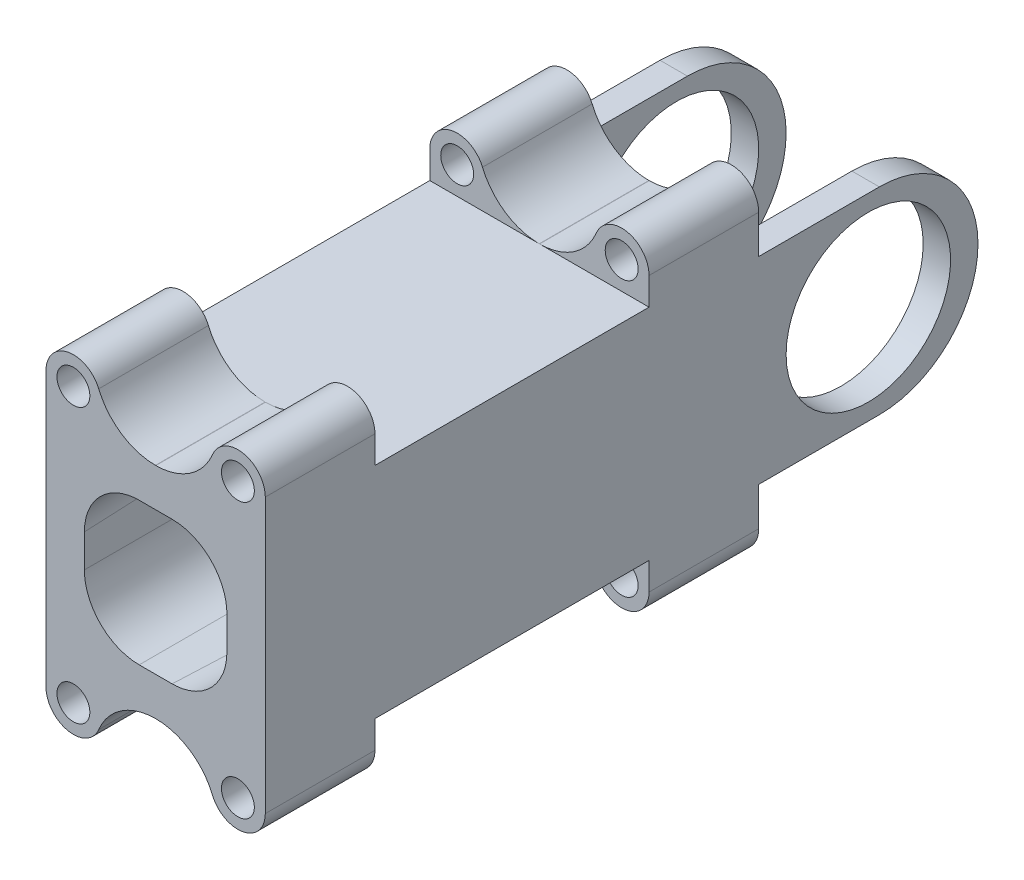
SolidWorks part; units mm, degrees
ref_plane "前视基准面" through (0, 0, 0) normal (0, 0, 1) x (1, 0, 0)
ref_plane "上视基准面" through (0, 0, 0) normal (0, 1, 0) x (1, 0, 0)
ref_plane "右视基准面" through (0, 0, 0) normal (1, 0, 0) x (0, 0, -1)
other "Configuration Table"
sketch "Sketch1" plane through (0, 0, 0) normal (0, 0, 1) x (1, 0, 0)
  line L1 (-10, -10) -> (10, -10)
  line L2 (-10, -10) -> (-10, 10)
  line L3 (-10, 10) -> (10, 10)
  line L4 (10, -10) -> (10, 10)
  line L5 (-10, -10) -> (10, 10) construction
  line L6 (-10, 10) -> (10, -10) construction
  point P0 (0, 0)
  dimension "D1" = 20
  dimension "D2" = 20
extrude "Boss-Extrude1" add sketch "Sketch1" along normal blind 15
sketch "Sketch3" plane through (0, 0, 0) normal (0, 0, -1) x (-1, 0, 0)
  line L0 (-10, 10) -> (0, 10) construction
  line L1 (-10, -10) -> (10, -10)
  line L2 (-10, -10) -> (-10, 10)
  line L3 (-10, 10) -> (10, 10)
  line L4 (10, -10) -> (10, 10)
  line L5 (-10, -10) -> (10, 10) construction
  line L6 (-10, 10) -> (10, -10) construction
  line L7 (0, 10) -> (-5, 10) construction
  line L8 (-5, 10) -> (-10, 10) construction
  line L9 (-10, 10) -> (-5, 10) construction
  line L10 (-5, 10) -> (-7.5, 10) construction
  line L11 (-7.5, 10) -> (-7.5, 12.5) construction
  line L12 (0, 0) -> (0, 10) construction
  line L13 (7.5, 10) -> (7.5, 12.5) construction
  line L14 (5, 10) -> (7.5, 10) construction
  line L15 (10, 10) -> (5, 10) construction
  line L16 (5, 10) -> (10, 10) construction
  line L17 (0, 0) -> (10, 0) construction
  line L18 (5, -10) -> (10, -10) construction
  line L19 (10, -10) -> (5, -10) construction
  line L20 (5, -10) -> (7.5, -10) construction
  line L21 (7.5, -10) -> (7.5, -12.5) construction
  line L22 (-7.5, -10) -> (-7.5, -12.5) construction
  line L23 (-5, -10) -> (-7.5, -10) construction
  line L24 (-10, -10) -> (-5, -10) construction
  line L25 (-5, -10) -> (-10, -10) construction
  line L26 (0, -10) -> (-5, -10) construction
  line L27 (-10, -10) -> (0, -10) construction
  line L28 (-10, -10) -> (10, -10)
  line L29 (-7.5, 12.5) -> (7.5, 12.5) construction
  line L30 (7.5, 12.5) -> (7.5, -12.5) construction
  line L31 (7.5, -12.5) -> (-7.5, -12.5) construction
  line L32 (-7.5, -12.5) -> (-7.5, 12.5) construction
  line L33 (-10, 10) -> (-10, 12.5)
  line L34 (-5, 12.5) -> (-5, 10)
  line L35 (5, 12.5) -> (5, 10)
  line L36 (10, 10) -> (10, 12.5)
  line L37 (10, -10) -> (10, -12.5)
  line L38 (5, -12.5) -> (5, -10)
  line L39 (-5, -12.5) -> (-5, -10)
  line L40 (-10, -10) -> (-10, -12.5)
  circle A0 centre (-7.5, 12.5) radius 1.5
  circle A1 centre (-7.5, 12.5) radius 2.5
  circle A6 centre (7.5, 12.5) radius 2.5
  circle A7 centre (7.5, 12.5) radius 1.5
  circle A8 centre (7.5, -12.5) radius 1.5
  circle A9 centre (7.5, -12.5) radius 2.5
  circle A14 centre (-7.5, -12.5) radius 2.5
  circle A15 centre (-7.5, -12.5) radius 1.5
  point P0 (0, 0)
  dimension "D1" = 3
  dimension "D2" = 5
  dimension "D3" = 2.5
extrude "Boss-Extrude2" add sketch "Sketch3" against normal blind 10
ref_plane "Plane1" through (0, 0, 45) normal (0, 0, 1) x (1, 0, 0)
sketch "Sketch7" plane through (0, 0, 45) normal (0, 0, 1) x (1, 0, 0)
  line L1 (-10, -10) -> (10, -10)
  line L2 (-10, -10) -> (-10, 10)
  line L3 (-10, 10) -> (10, 10)
  line L4 (10, -10) -> (10, 10)
  line L5 (-10, -10) -> (10, 10) construction
  line L6 (-10, 10) -> (10, -10) construction
  point P0 (0, 0)
  dimension "D1" = 20
  dimension "D2" = 20
sketch "Sketch8" plane through (0, 0, 15) normal (0, 0, 1) x (1, 0, 0)
  line L0 (-10, 10) -> (10, -10) construction
  line L1 (-10, -10) -> (10, -10)
  line L2 (-10, -10) -> (-10, 10)
  line L3 (-10, 10) -> (10, 10)
  line L4 (10, -10) -> (10, 10)
  line L5 (-10, -10) -> (10, 10) construction
  line L6 (-10, 10) -> (10, -10) construction
  point P0 (0, 0)
  point P7 (15, 15)
loft "Loft1" add profiles "Sketch7", "Sketch8"
sketch "Sketch9" plane through (0, 0, 45) normal (0, 0, 1) x (1, 0, 0)
  line L0 (0, 0) -> (8.25, 0) construction
  line L2 (0, 0) -> (0, 10) construction
  line L3 (6.5, 10) -> (10, 10)
  line L4 (6.5, 10) -> (6.5, -10)
  line L5 (6.5, -10) -> (10, -10)
  line L6 (10, 10) -> (10, -10)
  line L7 (6.5, 10) -> (10, -10) construction
  line L8 (6.5, -10) -> (10, 10) construction
  line L9 (10, 10) -> (-10, 10) construction
  line L10 (-6.5, -10) -> (-10, 10) construction
  line L11 (-6.5, 10) -> (-10, -10) construction
  line L12 (-10, 10) -> (-10, -10)
  line L13 (-6.5, -10) -> (-10, -10)
  line L14 (-6.5, 10) -> (-6.5, -10)
  line L15 (-6.5, 10) -> (-10, 10)
  dimension "D1" = 3.5
  dimension "D2" = 20
  dimension "D3" = 8.25
extrude "Boss-Extrude3" [suppressed] add sketch "Sketch9" along normal blind 10
sketch "Sketch11" plane through (0, 0, 0) normal (0, 0, 1) x (1, 0, 0)
  line L1 (-7.5, 7.5) -> (7.5, 7.5)
  line L2 (-7.5, 7.5) -> (-7.5, -7.5)
  line L3 (-7.5, -7.5) -> (7.5, -7.5)
  line L4 (7.5, 7.5) -> (7.5, -7.5)
  line L5 (-7.5, 7.5) -> (7.5, -7.5) construction
  line L6 (-7.5, -7.5) -> (7.5, 7.5) construction
  point P0 (0, 0)
  dimension "D1" = 15
  dimension "D2" = 15
sketch "Sketch12" plane through (0, 0, 45) normal (0, 0, 1) x (1, 0, 0)
  line L1 (-6.5, -6.5) -> (6.5, -6.5)
  line L2 (-6.5, -6.5) -> (-6.5, 6.5)
  line L3 (-6.5, 6.5) -> (6.5, 6.5)
  line L4 (6.5, -6.5) -> (6.5, 6.5)
  line L5 (-6.5, -6.5) -> (6.5, 6.5) construction
  line L6 (-6.5, 6.5) -> (6.5, -6.5) construction
  point P0 (0, 0)
  dimension "D1" = 13
  dimension "D2" = 13
loft "Cut-Loft1" cut profiles "Sketch11", "Sketch12"
sketch "Sketch14" [suppressed] plane through (-10, 0, 0) normal (-1, 0, 0) x (0, 0, 1)
  line L0 (55, 10) -> (55, -10) construction
  circle A0 centre (55, 0) radius 5
  dimension "D1" = 10
extrude "Cut-Extrude4" [suppressed] cut sketch "Sketch14" against normal through all
sketch "Sketch15" [suppressed] plane through (0, 0, 45) normal (0, 0, 1) x (1, 0, 0)
  line L0 (0, 6.5) -> (0, 10) construction
  line L1 (6.5, 6.5) -> (-6.5, 6.5) construction
  line L2 (10, 10) -> (-10, 10) construction
  line L3 (0, 10) -> (0, 8.25) construction
  line L4 (0, 0) -> (6.5, 0) construction
  line L5 (-10, 6.5) -> (10, 6.5)
  line L6 (-10, 6.5) -> (-10, 10)
  line L7 (-10, 10) -> (10, 10)
  line L8 (10, 6.5) -> (10, 10)
  line L9 (-10, 6.5) -> (10, 10) construction
  line L10 (-10, 10) -> (10, 6.5) construction
  line L11 (6.5, -6.5) -> (6.5, 6.5) construction
  line L12 (-10, -10) -> (10, -6.5) construction
  line L13 (-10, -6.5) -> (10, -10) construction
  line L14 (0, -10) -> (0, -8.25) construction
  line L15 (0, -6.5) -> (0, -10) construction
  line L16 (10, -6.5) -> (10, -10)
  line L17 (-10, -10) -> (10, -10)
  line L18 (-10, -6.5) -> (-10, -10)
  line L19 (-10, -6.5) -> (10, -6.5)
extrude "Boss-Extrude4" [suppressed] add sketch "Sketch15" along normal blind 10
sketch "Sketch16" [suppressed] plane through (0, -10, 0) normal (0, -1, 0) x (1, 0, 0)
  line L0 (-10, 55) -> (10, 55) construction
  circle A0 centre (0, 55) radius 5
  dimension "D1" = 10
extrude "Cut-Extrude5" [suppressed] cut sketch "Sketch16" against normal through all
sketch "Sketch19" plane through (0, 0, 0) normal (0, 0, -1) x (-1, 0, 0)
  line L0 (0, 0) -> (0, 22.1181) construction
  line L9 (0, 0) -> (10, 0) construction
  line L10 (10, 12.5) -> (10, -12.5) construction
  line L11 (10, 0) -> (7.5, 0) construction
  line L12 (7.5, 7.5) -> (7.5, -7.5) construction
  line L13 (7.5, 0) -> (8.75, 0) construction
  line L14 (-7.5, 9) -> (-10, -9) construction
  line L15 (7.5, -9) -> (10, -9)
  line L16 (7.5, -9) -> (7.5, 9)
  line L17 (7.5, 9) -> (10, 9)
  line L18 (10, -9) -> (10, 9)
  line L19 (7.5, -9) -> (10, 9) construction
  line L20 (7.5, 9) -> (10, -9) construction
  line L21 (-7.5, -9) -> (-10, 9) construction
  line L22 (-7.5, 0) -> (-8.75, 0) construction
  line L23 (-10, 0) -> (-7.5, 0) construction
  line L24 (-10, -9) -> (-10, 9)
  line L25 (-7.5, 9) -> (-10, 9)
  line L26 (-7.5, -9) -> (-7.5, 9)
  line L27 (-7.5, -9) -> (-10, -9)
  dimension "D1" = 18
extrude "Boss-Extrude6" add sketch "Sketch19" along normal blind 20
sketch "Sketch21" plane through (-10, 0, 0) normal (-1, 0, 0) x (0, 0, 1)
  line L0 (-20, 0) -> (-10, 0) construction
  line L1 (-20, -9) -> (-20, 9) construction
  circle A0 centre (-10, 0) radius 7.5
  dimension "D1" = 15
  dimension "D2" = 10
extrude "Cut-Extrude8" cut sketch "Sketch21" against normal through all contours A0
fillet "Fillet7" radius 9 4 edges at (-8.75, -9, -20) (-8.75, 9, -20) (8.75, -9, -20) (8.75, 9, -20)
sketch "Sketch23" plane through (0, 10, 0) normal (0, 1, 0) x (1, 0, 0)
  line L0 (0, 0) -> (0, -45) construction
  line L1 (5, 0) -> (-5, 0) construction
  line L2 (-55, -45) -> (55, -45) construction
  line L3 (0, -45) -> (0, -22.5) construction
  line L4 (0, -22.5) -> (10, -22.5) construction
  line L5 (10, -45) -> (10, -10) construction
ref_plane "Plane2" through (0, 0, 22.5) normal (0, 0, 1) x (1, 0, 0)
mirror "Mirror1" about plane through (0, 0, 22.5) normal (0, 0, 1) of "Boss-Extrude2"
fillet "Fillet8" radius 5 4 edges
fillet "Fillet9" radius 5.6 8 edges at (5, -10, 5) (-5, -10, 5) (5, 10, 5) (-5, 10, 5)
